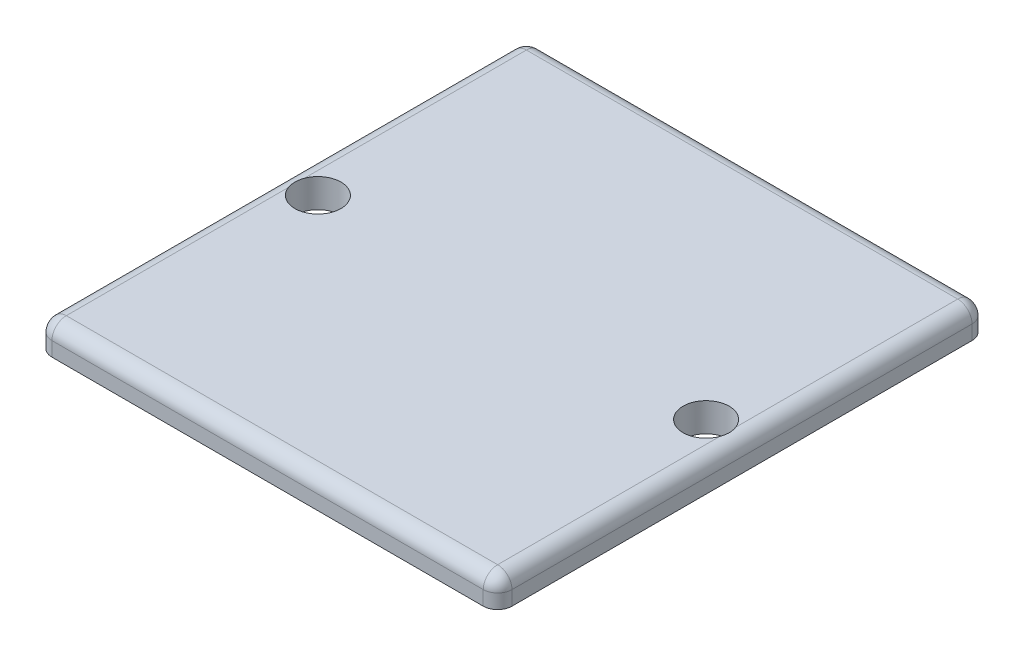
SolidWorks part; units mm, degrees
ref_plane "Front Plane" through (0, 0, 0) normal (0, 0, 1) x (1, 0, 0)
ref_plane "Top Plane" through (0, 0, 0) normal (0, 1, 0) x (1, 0, 0)
ref_plane "Right Plane" through (0, 0, 0) normal (1, 0, 0) x (0, 0, -1)
sketch "Sketch2" plane through (0, 0, 0) normal (0, 1, 0) x (1, 0, 0)
  line L0 (-16, 0) -> (16, 0) construction
  line L1 (-16, -17) -> (16, -17)
  line L2 (-16, -17) -> (-16, 17)
  line L3 (-16, 17) -> (16, 17)
  line L4 (16, -17) -> (16, 17)
  line L5 (-16, -17) -> (16, 17) construction
  line L6 (-16, 17) -> (16, -17) construction
  line L7 (0, 17) -> (0, -17) construction
  circle A0 centre (-13.5, 0) radius 1.6
  circle A1 centre (13.5, 0) radius 1.6
  point P0 (0, 0)
  point P14 (0, 0)
  dimension "D3" = 3.2
  dimension "D1" = 32
  dimension "D2" = 34
  dimension "D4" = 27
extrude "Boss-Extrude1" add sketch "Sketch2" along normal blind 2
fillet "Fillet1" radius 1 8 edges at (-16, 1, -17) (16, 1, -17) (16, 1, 17) (-16, 1, 17) (0, 2, 17) (-16, 2, 0) (0, 2, -17) (16, 2, 0)
